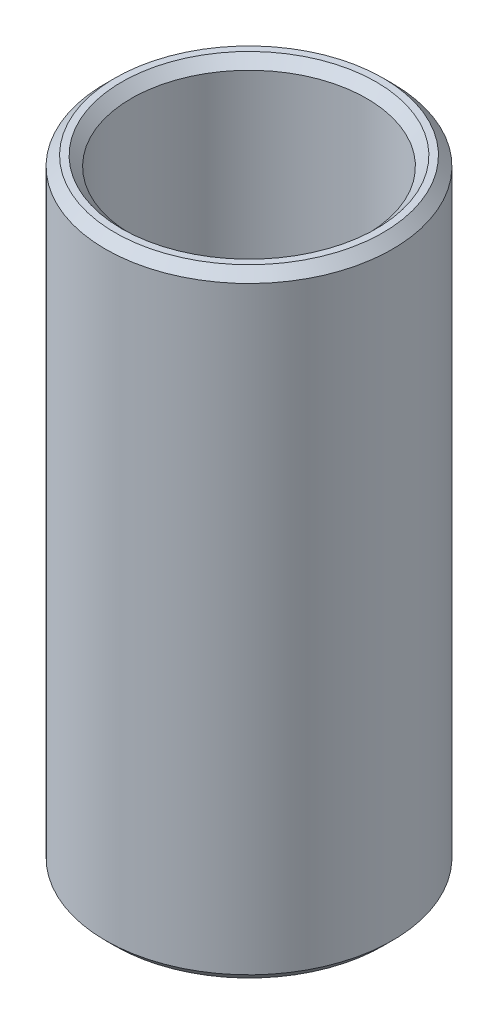
SolidWorks part; units mm, degrees
ref_plane "Front Plane" through (0, 0, 0) normal (0, 0, 1) x (1, 0, 0)
ref_plane "Top Plane" through (0, 0, 0) normal (0, 1, 0) x (1, 0, 0)
ref_plane "Right Plane" through (0, 0, 0) normal (1, 0, 0) x (0, 0, -1)
sketch "Sketch1" plane through (0, 0, 0) normal (0, 1, 0) x (1, 0, 0)
  circle A0 centre (0, 0) radius 22.5
  dimension "SLEEVE_OD" = 45
extrude "Boss-Extrude1" add sketch "Sketch1" along normal blind 96.852
sketch "Sketch2" plane through (0, 0, 0) normal (0, 1, 0) x (1, 0, 0)
  circle A0 centre (0, 0) radius 18.4524
  dimension "BORE_D" = 36.9048
extrude "Cut-Extrude1" cut sketch "Sketch2" along normal through all
chamfer "Chamfer1" distance 1.4938 angle 45 4 edges at (0, 96.852, 18.4524) (0, 0, 18.4524) (0, 0, 22.5) (0, 96.852, 22.5)
